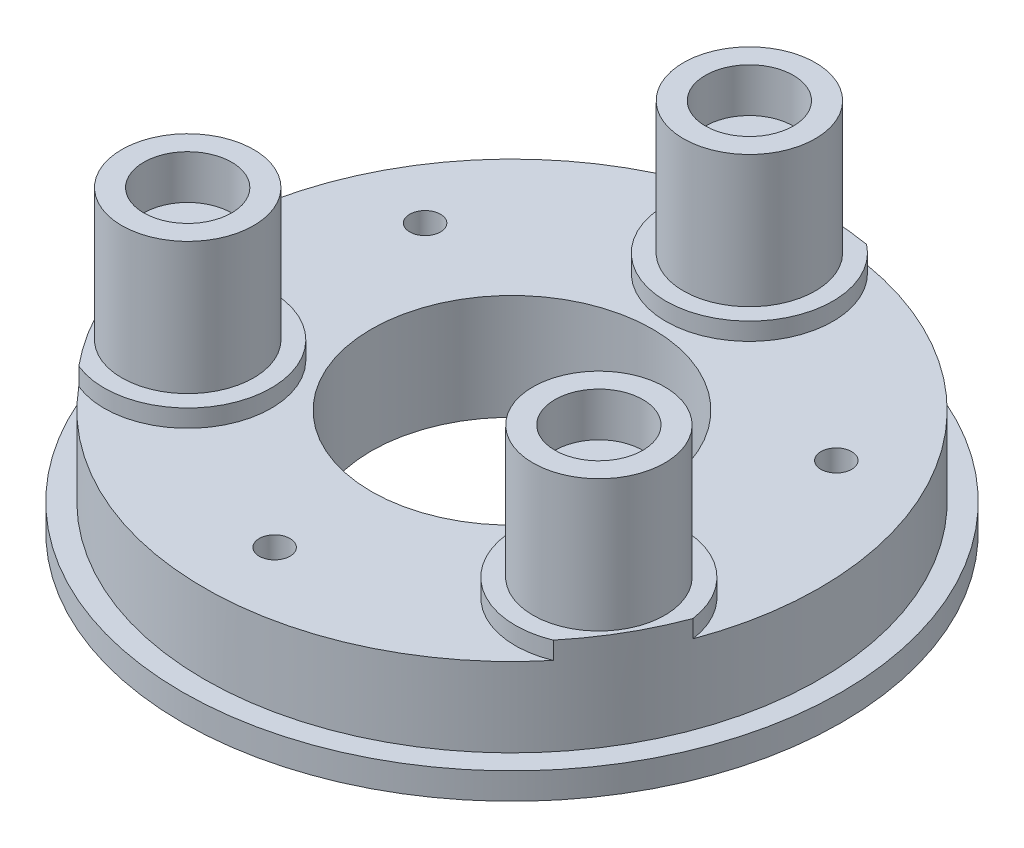
SolidWorks part; units mm, degrees
note: The reader was unsure of these and kept them because the rebuilt part matched: shared geometry of "Sketch1<3>".
ref_plane "Front Plane" through (0, 0, 0) normal (0, 0, 1) x (1, 0, 0)
ref_plane "Top Plane" through (0, 0, 0) normal (0, 1, 0) x (1, 0, 0)
ref_plane "Right Plane" through (0, 0, 0) normal (1, 0, 0) x (0, 0, -1)
sketch "Sketch1" plane through (0, 0, 0) normal (0, 1, 0) x (1, 0, 0)
  line L0 (0, 0) -> (0, 44.6523) construction
  circle A4 centre (0, 0) radius 37.5
  circle A5 centre (0, 0) radius 35
  arc A6 (-10.4425, 33.4059) -> (10.4425, 33.4059) centre (0, 30) ccw
  circle A7 centre (0, 0) radius 35
  arc A8 (34.1516, -7.6594) -> (23.7091, -25.7465) centre (25.9808, -15) ccw
  arc A9 (-23.7091, -25.7465) -> (-34.1516, -7.6594) centre (-25.9808, -15) ccw
  point P17 (0, 0)
  dimension "D1" = 75
  dimension "D2" = 70
  dimension "D3" = 30
  dimension "D4" = 3
extrude "Boss-Extrude1" add sketch "Sketch1" along normal blind 3 contours A4
extrude "Boss-Extrude2" add sketch "Sketch1<3>" along normal blind 12
sketch "Sketch1<3>" plane through (0, 0, 0) normal (0, 1, 0) x (1, 0, 0) same geometry as "Sketch1"
sketch "Sketch13" plane through (0, 12, 0) normal (0, 1, 0) x (1, 0, 0)
  circle A0 centre (0, 0) radius 16
  dimension "D1" = 32
extrude "Cut-Extrude6" cut sketch "Sketch13" against normal through all
sketch "Sketch24" plane through (0, 12, 0) normal (0, 1, 0) x (1, 0, 0)
  line L0 (0, 0) -> (0, 27.027) construction
  arc A0 (-5.813, 34.5139) -> (5.813, 34.5139) centre (0, 27) ccw
  circle A1 centre (0, 0) radius 35
  arc A2 (32.7964, -12.2227) -> (26.9834, -22.2912) centre (23.3827, -13.5) ccw
  arc A3 (-26.9834, -22.2912) -> (-32.7964, -12.2227) centre (-23.3827, -13.5) ccw
  point P15 (0, 0)
  dimension "D1" = 19
  dimension "D4" = 70
  dimension "D2" = 27
  dimension "D3" = 3
extrude "Boss-Extrude9" add sketch "Sketch24" along normal blind 2
sketch "Sketch25" plane through (0, 14, 0) normal (0, 1, 0) x (1, 0, 0)
  line L0 (0, 0) -> (0, 55.8426) construction
  circle A0 centre (0, 27) radius 7.5
  circle A1 centre (23.3827, -13.5) radius 7.5
  circle A2 centre (-23.3827, -13.5) radius 7.5
  point P11 (0, 0)
  dimension "D2" = 15
  dimension "D1" = 27
  dimension "D3" = 3
extrude "Boss-Extrude10" add sketch "Sketch25" along normal blind 15
sketch "Sketch26" plane through (0, 29, 0) normal (0, 1, 0) x (1, 0, 0)
  line L0 (0, 0) -> (0, 38.3857) construction
  circle A0 centre (0, 27) radius 5
  circle A1 centre (23.3827, -13.5) radius 5
  circle A2 centre (-23.3827, -13.5) radius 5
  point P11 (0, 0)
  dimension "D2" = 10
  dimension "D1" = 27
  dimension "D3" = 3
extrude "Cut-Extrude9" cut sketch "Sketch26" against normal blind 5
hole_wizard "CBORE for M3 Pan Head Machine Screw1" positions "Sketch27" profile "Sketch28" counterbore size "M3" standard "ANSI Metric" end condition through all
sketch "Sketch27" plane through (0, 0, 0) normal (0, -1, 0) x (-1, 0, 0)
  point P0 (0, 27)
  point P9 (23.3827, -13.5)
  point P10 (-23.3827, -13.5)
  dimension "D1" = 27
  dimension "D2" = 3
sketch "Sketch28" plane through (0, 0, -27) normal (1, 0, 0) x (0, 0, -1)
  line L0 (0, 0) -> (0, 29)
  line L1 (0, 29) -> (1.8, 29)
  line L3 (1.8, 29) -> (1.8, 2.4)
  line L4 (3.5, 2.4) -> (1.8, 2.4)
  line L5 (3.5, 2.4) -> (3.5, 0.025)
  line L6 (3.5, 0.025) -> (3.525, 0)
  line L7 (3.525, 0) -> (0, 0)
  line L8 (-3.5, 0.025) -> (-3.525, 0) construction
  line L11 (0, -6.35) -> (0, 107.95) construction
  dimension "Thru Hole Dia." = 3.6
  dimension "Thru Hole Depth" = 29
  dimension "C'Bore Dia." = 7
  dimension "C'Bore Depth" = 2.4
  dimension "Near C'Sink Dia." = 7.05
  dimension "Near C'Sink Angle" = 90
sketch "Sketch29" plane through (0, 12, 0) normal (0, 1, 0) x (1, 0, 0)
  line L0 (0, 0) -> (23.3827, 13.5) construction
  line L1 (0, 0) -> (0, 14.4601) construction
  circle A0 centre (23.3827, 13.5) radius 1.75
  circle A1 centre (0, -27) radius 1.75
  circle A2 centre (-23.3827, 13.5) radius 1.75
  point P11 (0, 0)
  dimension "D3" = 3.5
  dimension "D1" = 60
  dimension "D2" = 27
  dimension "D4" = 3
extrude "Cut-Extrude10" cut sketch "Sketch29" against normal through all
